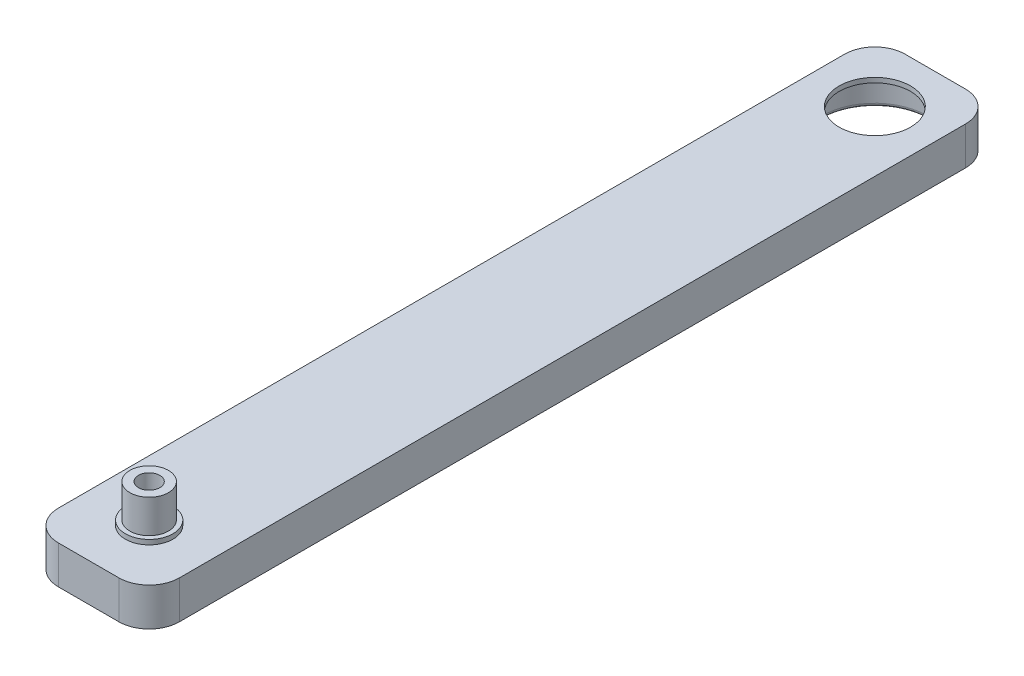
SolidWorks part; units mm, degrees
ref_plane "Front Plane" through (0, 0, 0) normal (0, 0, 1) x (1, 0, 0)
ref_plane "Top Plane" through (0, 0, 0) normal (0, 1, 0) x (1, 0, 0)
ref_plane "Right Plane" through (0, 0, 0) normal (1, 0, 0) x (0, 0, -1)
sketch "Sketch1" plane through (0, 0, 0) normal (0, 1, 0) x (1, 0, 0)
  line L1 (-12.7, -88.9) -> (12.7, -88.9)
  line L2 (-12.7, -88.9) -> (-12.7, 88.9)
  line L3 (-12.7, 88.9) -> (12.7, 88.9)
  line L4 (12.7, -88.9) -> (12.7, 88.9)
  line L5 (-12.7, -88.9) -> (12.7, 88.9) construction
  line L6 (-12.7, 88.9) -> (12.7, -88.9) construction
  point P0 (0, 0)
  dimension "D1" = 25.4
  dimension "D2" = 177.8
extrude "Boss-Extrude1" add sketch "Sketch1" along normal mid plane 8
fillet "Fillet1" radius 6.35 4 edges at (12.7, 0, -88.9) (-12.7, 0, -88.9) (12.7, 0, 88.9) (-12.7, 0, 88.9)
sketch "Sketch2" plane through (0, 4, 0) normal (0, 1, 0) x (1, 0, 0)
  line L0 (0, 76.2) -> (0, 88.9) construction
  line L1 (6.35, 88.9) -> (-6.35, 88.9) construction
  circle A0 centre (0, 76.2) radius 11.05
  dimension "D2" = 22.1
  dimension "D1" = 12.7
extrude "Cut-Extrude1" cut sketch "Sketch2" against normal through all
fillet "Fillet2" radius 0.7937 1 edges at (0, -4, -65.15)
sketch "Sketch3" plane through (0, 4, 0) normal (0, 1, 0) x (1, 0, 0)
  line L0 (0, 0) -> (50000, 0) construction
  circle A0 centre (0, -76.2) radius 2.25
  circle A3 centre (0, 76.2) radius 11.05 construction
  point P2 (0, 0)
  point P5 (0, 0)
  point P8 (0, 76.2)
  dimension "D1" = 4.5
extrude "Cut-Extrude2" cut sketch "Sketch3" against normal through all
sketch "Sketch4" plane through (0, 4, 0) normal (0, 1, 0) x (1, 0, 0)
  circle A0 centre (0, -76.2) radius 5
  circle M2 centre (0, -76.2) radius 2.25
  dimension "D1" = 10
extrude "Boss-Extrude2" add sketch "Sketch4" along normal blind 1 contours A0 M2 region at (-4.8586, 4, 76.2)
sketch "Sketch6" plane through (0, 4, 0) normal (0, 1, 0) x (1, 0, 0)
  circle A0 centre (0, 76.2) radius 11.05 construction
  circle A1 centre (0, 76.2) radius 11.05
extrude "Boss-Extrude3" add sketch "Sketch6" against normal offset from surface (1 mm away) 7 up to face at (0, -4, 78.45)
sketch "Sketch7" plane through (0, 3, 0) normal (0, -1, 0) x (1, 0, 0)
  circle A0 centre (0, -76.2) radius 7.5
  circle A1 centre (0, -76.2) radius 11.05 construction
  dimension "D1" = 15
extrude "Cut-Extrude3" cut sketch "Sketch7" against normal through all
sketch "Sketch8" plane through (0, 5, 0) normal (0, 1, 0) x (1, 0, 0)
  circle A0 centre (0, -76.2) radius 4.05
  circle M1 centre (0, -76.2) radius 2.25
  dimension "D1" = 8.1
extrude "Boss-Extrude4" add sketch "Sketch8" along normal blind 7 contours A0 M1 region at (-3.9354, 5, 76.2)
